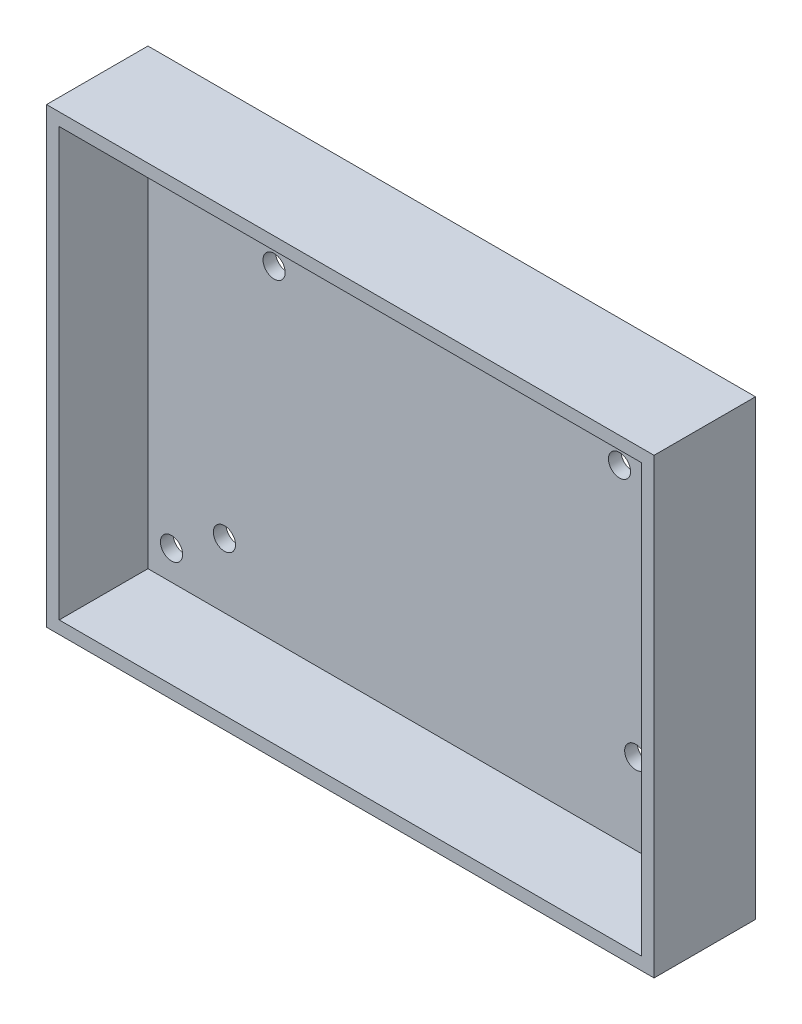
SolidWorks part; units mm, degrees
ref_plane "Front Plane" through (0, 0, 0) normal (0, 0, 1) x (1, 0, 0)
ref_plane "Top Plane" through (0, 0, 0) normal (0, 1, 0) x (1, 0, 0)
ref_plane "Right Plane" through (0, 0, 0) normal (1, 0, 0) x (0, 0, -1)
sketch "Sketch1" plane through (0, 0, 0) normal (0, 0, 1) x (1, 0, 0)
  line L0 (259.442, -1.577) -> (291.442, -1.577)
  line L1 (35.7326, 96.8459) -> (291.442, 96.8459)
  line L2 (35.7326, 96.8459) -> (35.7326, -100)
  line L3 (35.7326, -100) -> (291.442, -100)
  line L4 (291.442, 96.8459) -> (291.442, -100)
  line L5 (67.7326, 69.8459) -> (259.442, 69.8459)
  line L6 (67.7326, 69.8459) -> (67.7326, -73)
  line L7 (67.7326, -73) -> (259.442, -73)
  line L8 (259.442, 69.8459) -> (259.442, -73)
  line L9 (163.5873, -73) -> (163.5873, -100)
  line L11 (71.7326, -69) -> (255.442, -69)
  line L12 (71.7326, -69) -> (71.7326, 65.8459)
  line L13 (71.7326, 65.8459) -> (255.442, 65.8459)
  line L14 (255.442, -69) -> (255.442, 65.8459)
  circle A0 centre (94.9732, 44.7663) radius 3.5
  circle A1 centre (111.547, 33.5721) radius 3.5
  circle A2 centre (220.5289, 33.686) radius 3.5
  circle A3 centre (237.2169, 44.7092) radius 3.5
  circle A4 centre (225.662, -43.5036) radius 3.5
  circle A5 centre (242.2358, -54.6978) radius 3.5
  circle A6 centre (95.871, -48.657) radius 3.5
  circle A7 centre (79.1831, -59.6802) radius 3.5
  circle A8 centre (94.9732, 44.7663) radius 3.5 construction
  circle A9 centre (111.547, 33.5721) radius 3.5 construction
  circle A10 centre (220.5289, 33.686) radius 3.5 construction
  circle A11 centre (237.2169, 44.7092) radius 3.5 construction
  circle A12 centre (225.662, -43.5036) radius 3.5 construction
  circle A13 centre (242.2358, -54.6978) radius 3.5 construction
  circle A14 centre (95.871, -48.657) radius 3.5 construction
  circle A15 centre (79.1831, -59.6802) radius 3.5 construction
  dimension "D1" = 27
  dimension "D2" = 32
  dimension "D3" = 4
  dimension "D4" = 4
  dimension "D5" = 4
  dimension "D6" = 4
extrude "Boss-Extrude2" add sketch "Sketch1" along normal blind 4 contours L11 L14 L13 L12 A7 A6 A5 A4 A3 A2 A1 A0 | L8 L5 L6 L7 L14 L11 L12 L13 region at (257.0512, -37.2885, 0) region at (163.5897, -1.5185, 0)
extrude "Boss-Extrude3" add sketch "Sketch1<5>" along normal blind 32 contours L8 L5 L6 L7 L14 L11 L12 L13 region at (257.0512, -37.2885, 0)
sketch "Sketch1<5>" plane through (0, 0, 0) normal (0, 0, 1) x (1, 0, 0) same geometry as "Sketch1"
